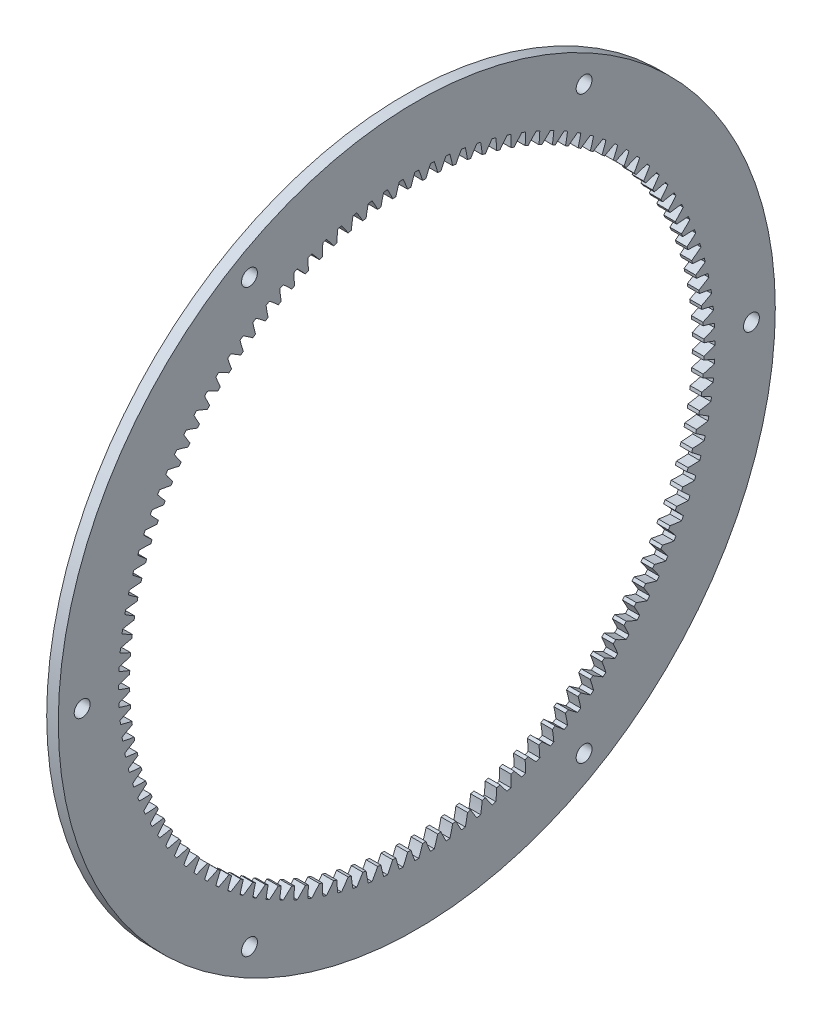
SolidWorks part; units mm, degrees
ref_plane "Plane1" through (0, 0, 0) normal (0, 0, 1) x (1, 0, 0)
ref_plane "Plane2" through (0, 0, 0) normal (0, 1, 0) x (1, 0, 0)
ref_plane "Plane3" through (0, 0, 0) normal (1, 0, 0) x (0, 0, -1)
sketch "HoldingSke" plane through (0, 0, 0) normal (0, 1, 0) x (1, 0, 0)
  line L0 (0, 0) -> (-0.25, -0.433)
  line L1 (-15, 0) -> (100, 0) construction
  line L2 (0, 0) -> (-2.1039, 2.3779)
  line L3 (0, 0) -> (-11.863, 4.5341)
  line L4 (0, 0) -> (-4.318, 7.479)
  line L5 (0, 0) -> (-23.7986, -8.8762)
  line L6 (0, 0) -> (-10.5278, -7.1032)
  line L7 (-2.1039, 2.3779) -> (3.3635, 27.1825)
  line L8 (-76.2, 4.3779) -> (-54.61, 4.3779)
  line L9 (-71.009, 38.7566) -> (-53.1078, 45.2721)
  line L10 (-76.2, 71.12) -> (104.1128, 71.12)
  line L11 (0, 0) -> (-4.7625, 0)
  line L12 (-76.2, 101.6) -> (-76.133, 101.6)
  line L13 (24.9733, 27.94) -> (52.9518, 28.4284)
  line L14 (24.9733, 27.94) -> (24.9743, 27.94)
  line L15 (24.9733, 27.94) -> (100.4006, 29.5858)
  circle A0 centre (0, 0) radius 147.32
  circle A1 centre (0, 0) radius 12.7
  circle A2 centre (0, 0) radius 12.7
  dimension "MHD" = 25.4
  dimension "Hub_dia" = 25.4
  dimension "Diameter" = 294.64
  dimension "Num_teeth" = 120
  dimension "Pitch_radius" = 180.3128
  dimension "Pitch" = 0.5
  dimension "Width" = 4.7625
  dimension "Overall_len" = 25.4
  dimension "Show_teeth" = 120
  dimension "Thickness" = 12.7
  dimension "OAL" = 25.4001
  dimension "T_dim" = 21.59
  dimension "Ap" = 20
  dimension "H" = 19.05
  dimension "Backlash" = 0.067
  dimension "Addendum_fac" = 1
  dimension "Dedendum_fac" = 1.25
  dimension "Clearance_fac" = 0.25
  dimension "Dedendum_add" = 0.001
  dimension "Module" = 2
sketch "BasProSke" plane through (0, 0, 0) normal (0, 1, 0) x (1, 0, 0)
  line L0 (-10, 0) -> (60, 0) construction
  line L1 (0, 118) -> (0, 147.32)
  line L2 (0, 118) -> (4.7625, 118)
  line L3 (4.7625, 118) -> (4.7625, 147.32)
  line L4 (4.7625, 147.32) -> (0, 147.32)
  dimension "Diameter" = 294.64
  dimension "Thickness" = 4.7625
  dimension "Inside_diameter" = 236
revolve "Base-Revolve" add sketch "BasProSke" angle 360 about L0
sketch "TooCutSke" plane through (0, 0, 0) normal (1, 0, 0) x (0, 0, -1)
  line L3 (1.7383, 119.9874) -> (1.7383, 53.6633) construction
  line L4 (0, 0) -> (0, 59.563) construction
  line L5 (0, 0) -> (-1.7886, 68.3041) construction
  line L6 (-54.8647, 100.0849) -> (35.1732, 102.4426) construction
  circle A0 centre (0, 0) radius 120 construction
  circle A1 centre (0, 0) radius 122.501 construction
  circle A2 centre (0, 0) radius 101.4868 construction
  circle A3 centre (0, 0) radius 117.9746 construction
  arc A4 (2.414, 117.9499) -> (0.7917, 122.4984) centre (-54.8647, 100.0849) ccw
  arc A5 (2.414, 117.9499) -> (-2.414, 117.9499) centre (0, 0) ccw
  arc A6 (0.7917, 122.4984) -> (-0.7917, 122.4984) centre (0, 0) ccw
  arc A7 (-0.7917, 122.4984) -> (-2.414, 117.9499) centre (54.8647, 100.0849) ccw
  dimension "Pitch_dia" = 240
  dimension "Base_dia" = 202.9736
  dimension "Root_dia" = 245.002
  dimension "Overcut_dia" = 235.9492
  dimension "Flank_rad" = 60
  dimension "Half_ang" = 1.5
  dimension "Half_CT" = 1.7383
extrude "ToothCut" cut sketch "TooCutSke" along normal through all
fillet "Breaks" [suppressed] radius 0.2
fillet "RootFillets" [suppressed] radius 0.501
pattern_circular "TeethCuts" count 120 every 3 about axis through (-10, 0, 0) along (1, 0, 0) of "RootFillets", "Breaks", "ToothCut"
sketch "Sketch1" plane through (4.7625, 0, 0) normal (1, 0, 0) x (0, 0, -1)
  line L1 (0, 158.7713) -> (-137.5, 79.3857) construction
  line L2 (-137.5, 79.3857) -> (-137.5, -79.3857) construction
  line L3 (-137.5, -79.3857) -> (0, -158.7713) construction
  line L4 (0, -158.7713) -> (137.5, -79.3857) construction
  line L5 (137.5, -79.3857) -> (137.5, 79.3857) construction
  line L6 (137.5, 79.3857) -> (0, 158.7713) construction
  circle A0 centre (0, 0) radius 137.5 construction
  circle A1 centre (-68.75, 119.0785) radius 3.2639
  circle A2 centre (68.75, 119.0785) radius 3.2639
  circle A3 centre (137.5, 0) radius 3.2639
  circle A4 centre (68.75, -119.0785) radius 3.2639
  circle A5 centre (-68.75, -119.0785) radius 3.2639
  circle A6 centre (-137.5, 0) radius 3.2639
  point P23 (0, 0)
  dimension "D2" = 6.5278
  dimension "D4" = 137.5
  dimension "D1" = 158.7713
  dimension "D3" = 6
extrude "Cut-Extrude1" cut sketch "Sketch1" against normal through all
equation "' \"Module@HoldingSke\" = 6.35"
equation "' \"Num_teeth@HoldingSke\" = 24"
equation "' \"Ap@HoldingSke\" =  14.5"
equation "' \"Width@HoldingSke\" = 12"
equation "' \"Diameter@HoldingSke\" = 8 * 25.4"
equation "' \"Show_teeth@HoldingSke\" = 100"
equation "' \"Backlash@HoldingSke\" = 0.009 * 25.4"
equation "' \"Addendum_fac@HoldingSke\" = 1.0"
equation "' \"Dedendum_fac@HoldingSke\" = 1.25"
equation "' \"Dedendum_add@HoldingSke\" = 0.00005 * 25.4"
equation "' \"Clearance_fac@HoldingSke\" = 0.25"
equation "\"Pitch@HoldingSke\" = 1 / \"Module@HoldingSke\" "
equation "\"Overcut_dia@TooCutSke\" = (\"Num_teeth@HoldingSke\" - 2 * \"Addendum_fac@HoldingSke\") / \"Pitch@HoldingSke\" - 0.002 * 25.4"
equation "\"Pitch_dia@TooCutSke\" = \"Num_teeth@HoldingSke\" / \"Pitch@HoldingSke\""
equation "\"Base_dia@TooCutSke\" = \"Num_teeth@HoldingSke\" / \"Pitch@HoldingSke\" * cos((\"Ap@HoldingSke\"  * 3.14159265 / 180)) * 0.90"
equation "\"Root_dia@TooCutSke\" = \"Num_teeth@HoldingSke\"  / \"Pitch@HoldingSke\" + 2 *  \"Dedendum_fac@HoldingSke\"/ \"Pitch@HoldingSke\" + \"Dedendum_add@HoldingSke\" * 2"
equation "\"Half_ang@TooCutSke\" = 180 / \"Num_teeth@HoldingSke\""
equation "\"Half_CT@TooCutSke\" = \"Num_teeth@HoldingSke\" / \"Pitch@HoldingSke\" * sin((3.14159265 / 2 / \"Num_teeth@HoldingSke\")) / 2 + 10 * \"Backlash@HoldingSke\" / 4"
equation "\"Flank_rad@TooCutSke\" = \"Num_teeth@HoldingSke\" / \"Pitch@HoldingSke\" / 4"
equation "\"Radius@RootFillets\"= \"Clearance_fac@HoldingSke\" / \"Pitch@HoldingSke\" + \"Dedendum_add@HoldingSke\""
equation "\"Break_rad@Breaks\" = 0.02 / \"Pitch@HoldingSke\" * 5"
equation "\"Num_teeth@TeethCuts\" = int( \"Show_teeth@HoldingSke\" ) + 1"
equation "\"Num_teeth@TeethCuts\" = ((sgn( \"Num_teeth@TeethCuts\" - \"Num_teeth@HoldingSke\" )-1)*( \"Num_teeth@TeethCuts\" - \"Num_teeth@HoldingSke\" ))/-2+ \"Num_teeth@HoldingSke\""
equation "\"Num_teeth@TeethCuts\" = ((sgn( \"Num_teeth@TeethCuts\" - 2.0)+1)*( \"Num_teeth@TeethCuts\" - 2.0))/2 +2.0"
equation "\"Angle@TeethCuts\" = 360.0 / \"Num_teeth@HoldingSke\""
equation "\"Diameter@BasProSke\" = \"Num_teeth@HoldingSke\"  / \"Pitch@HoldingSke\" + 2 *  \"Dedendum_fac@HoldingSke\"/ \"Pitch@HoldingSke\" + \"Dedendum_add@HoldingSke\" * 2 + 0.002 * 25.4"
equation "\"Diameter@BasProSke\" = ((sgn( \"Diameter@BasProSke\"  - \"Diameter@HoldingSke\" )+1)*( \"Diameter@BasProSke\"  - \"Diameter@HoldingSke\" ))/2 + \"Diameter@HoldingSke\""
equation "\"Inside_diameter@BasProSke\" =  (\"Num_teeth@HoldingSke\" - 2 * \"Addendum_fac@HoldingSke\") / \"Pitch@HoldingSke\" "
equation "\"Thickness@BasProSke\"  = \"Width@HoldingSke\""
equation "\"D1@Sketch1\"=6.25083953in"
